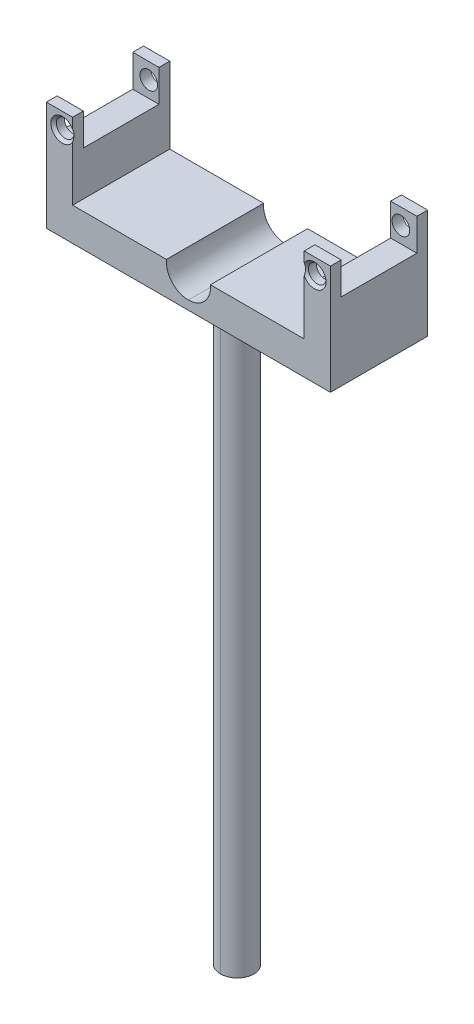
SolidWorks part; units mm, degrees
ref_plane "Front Plane" through (0, 0, 0) normal (0, 0, 1) x (1, 0, 0)
ref_plane "Top Plane" through (0, 0, 0) normal (0, 1, 0) x (1, 0, 0)
ref_plane "Right Plane" through (0, 0, 0) normal (1, 0, 0) x (0, 0, -1)
sketch "Sketch3" plane through (0, 0, 0) normal (0, 0, 1) x (1, 0, 0)
  line L0 (0, 0) -> (0, 19.8)
  line L1 (0, 19.8) -> (4.7504, 19.8)
  line L2 (4.7504, 19.8) -> (4.7504, 6)
  line L3 (4.7504, 6) -> (21.75, 6)
  line L4 (0, 0) -> (25.731, 0)
  line L5 (25.731, 0) -> (25.731, 1.615)
  arc A0 (21.75, 6) -> (25.731, 1.615) centre (25.7314, 5.615) ccw
extrude "Boss-Extrude1" add sketch "Sketch3" along normal blind 17.6
sketch "Sketch4" plane through (0, 19.8, 0) normal (0, 1, 0) x (1, 0, 0)
  line L0 (4.7504, -17.6) -> (4.7504, 0) construction
  line L1 (0, -1.95) -> (4.7504, -1.95)
  line L2 (0, -1.95) -> (0, -15.65)
  line L3 (0, -15.65) -> (4.7504, -15.65)
  line L4 (4.7504, -1.95) -> (4.7504, -15.65)
  line L5 (4.7504, 0) -> (0, 0) construction
  dimension "D1" = 4.7504
  dimension "D2" = 13.7
  dimension "D3" = 1.95
extrude "Cut-Extrude1" cut sketch "Sketch4" against normal blind 5.8
sketch "Sketch5" plane through (0, 0, 0) normal (0, 0, -1) x (-1, 0, 0)
  line L0 (0, 19.8) -> (0, 0) construction
  line L1 (-4.7504, 19.8) -> (0, 19.8) construction
  circle A0 centre (-2.9, 16.9) radius 1.6
  dimension "D1" = 3.2
  dimension "D2" = 2.9
  dimension "D3" = 2.9
extrude "Cut-Extrude2" cut sketch "Sketch5" against normal blind 17.8
sketch "Sketch6" plane through (0, 0, 0) normal (0, -1, 0) x (1, 0, 0)
  line L0 (25.731, 17.6) -> (25.731, 0) construction
  line L1 (25.731, 11.7998) -> (25.731, 5.8005)
  arc A0 (25.731, 11.7998) -> (25.731, 5.8005) centre (25.6846, 8.8001) ccw
  dimension "D1" = 8.8
extrude "Boss-Extrude2" add sketch "Sketch6" along normal blind 107
fillet "Fillet1" radius 4 1 edges at (22.6846, 0, 8.8001)
chamfer "Chamfer1" distance 0.5 angle 45 1 edges at (4.5, 16.9, 17.6)
mirror "Mirror4" about plane through (25.731, 0, 17.6) normal (-1, 0, 0) of bodies 104
